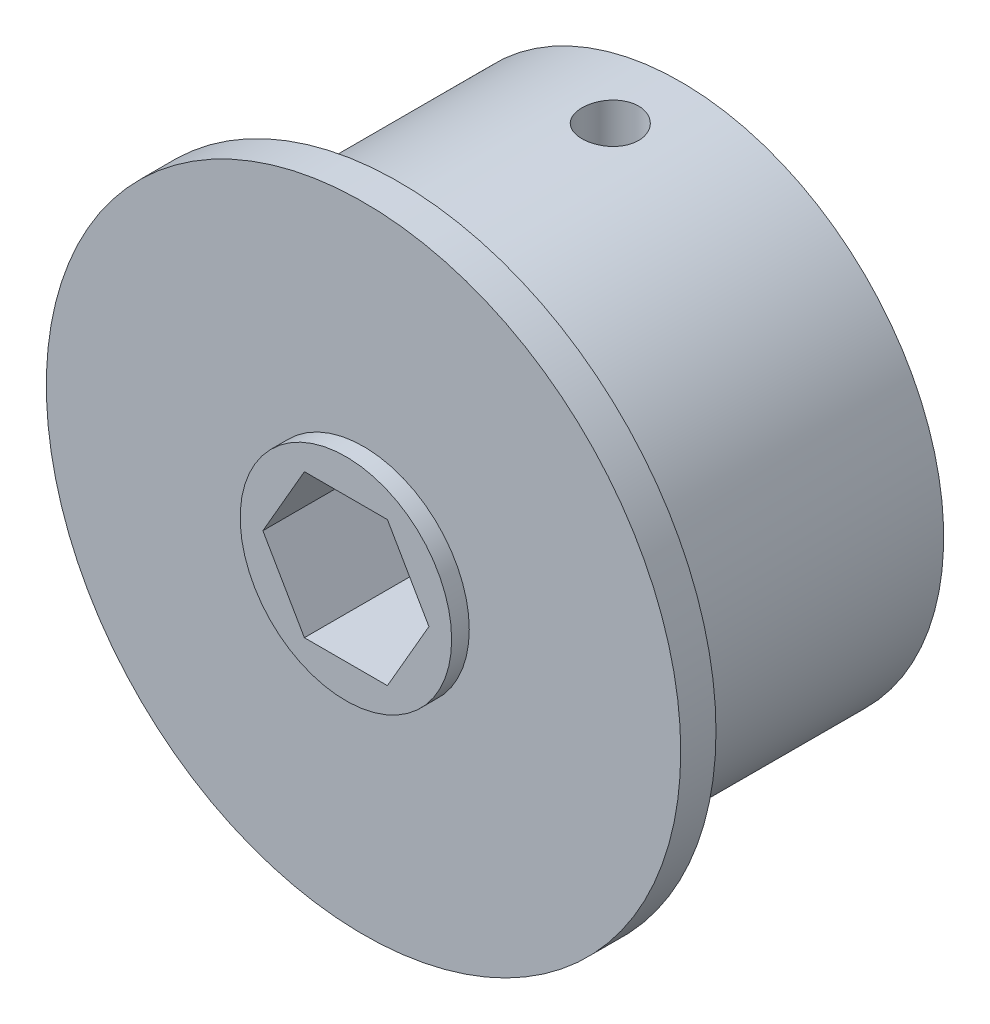
SolidWorks part; units mm, degrees
material "PET"
ref_plane "Front Plane" through (0, 0, 0) normal (0, 0, 1) x (1, 0, 0)
ref_plane "Top Plane" through (0, 0, 0) normal (0, 1, 0) x (1, 0, 0)
ref_plane "Right Plane" through (0, 0, 0) normal (1, 0, 0) x (0, 0, -1)
sketch "Sketch1" plane through (0, 0, 0) normal (0, 0, 1) x (1, 0, 0)
  line L1 (7.479, 0) -> (3.7395, 6.477)
  line L2 (3.7395, 6.477) -> (-3.7395, 6.477)
  line L3 (-3.7395, 6.477) -> (-7.479, 0)
  line L4 (-7.479, 0) -> (-3.7395, -6.477)
  line L5 (-3.7395, -6.477) -> (3.7395, -6.477)
  line L6 (3.7395, -6.477) -> (7.479, 0)
  circle A0 centre (0, 0) radius 23.6855
  circle A1 centre (0, 0) radius 6.477 construction
  dimension "D1" = 47.371
  dimension "D2" = 12.954
extrude "Boss-Extrude1" add sketch "Sketch1" along normal blind 12.7
sketch "Sketch2" plane through (0, 0, 12.7) normal (0, 0, 1) x (1, 0, 0)
  line L0 (3.7395, -6.477) -> (7.479, 0) construction
  line L1 (7.479, 0) -> (3.7395, 6.477)
  line L2 (3.7395, 6.477) -> (-3.7395, 6.477)
  line L3 (-3.7395, 6.477) -> (-7.479, 0)
  line L4 (-7.479, 0) -> (-3.7395, -6.477)
  line L5 (-3.7395, -6.477) -> (3.7395, -6.477)
  line L6 (3.7395, -6.477) -> (7.479, 0)
  circle A0 centre (0, 0) radius 28.575
  circle A1 centre (0, 0) radius 6.477 construction
  dimension "D1" = 57.15
extrude "Boss-Extrude2" add sketch "Sketch2" along normal blind 3.175
sketch "Sketch3" plane through (0, 0, 0) normal (0, 0, -1) x (-1, 0, 0)
  circle A0 centre (0, 0) radius 23.6855
extrude "Boss-Extrude3" add sketch "Sketch3" along normal blind 12.7
sketch "Sketch4" plane through (0, 0, 0) normal (0, 1, 0) x (1, 0, 0)
  circle A0 centre (0, 6.35) radius 2.5527
  dimension "D1" = 5.1054
  dimension "D2" = 6.35
extrude "Cut-Extrude1" cut sketch "Sketch4" against normal through all both and the other way through all
sketch "Sketch5" plane through (0, 0, 15.875) normal (0, 0, 1) x (1, 0, 0)
  line L0 (3.7395, -6.477) -> (7.479, 0) construction
  line L1 (7.479, 0) -> (3.7395, 6.477)
  line L2 (3.7395, 6.477) -> (-3.7395, 6.477)
  line L3 (-3.7395, 6.477) -> (-7.479, 0)
  line L4 (-7.479, 0) -> (-3.7395, -6.477)
  line L5 (-3.7395, -6.477) -> (3.7395, -6.477)
  line L6 (3.7395, -6.477) -> (7.479, 0)
  line L7 (3.7395, -6.477) -> (7.479, 0) construction
  circle A0 centre (0, 0) radius 9.525
  circle A1 centre (0, 0) radius 6.477 construction
  point P3 (7.479, 0)
  point P15 (3.7395, 6.477)
  dimension "D1" = 19.05
extrude "Boss-Extrude4" add sketch "Sketch5" along normal blind 1.5875
